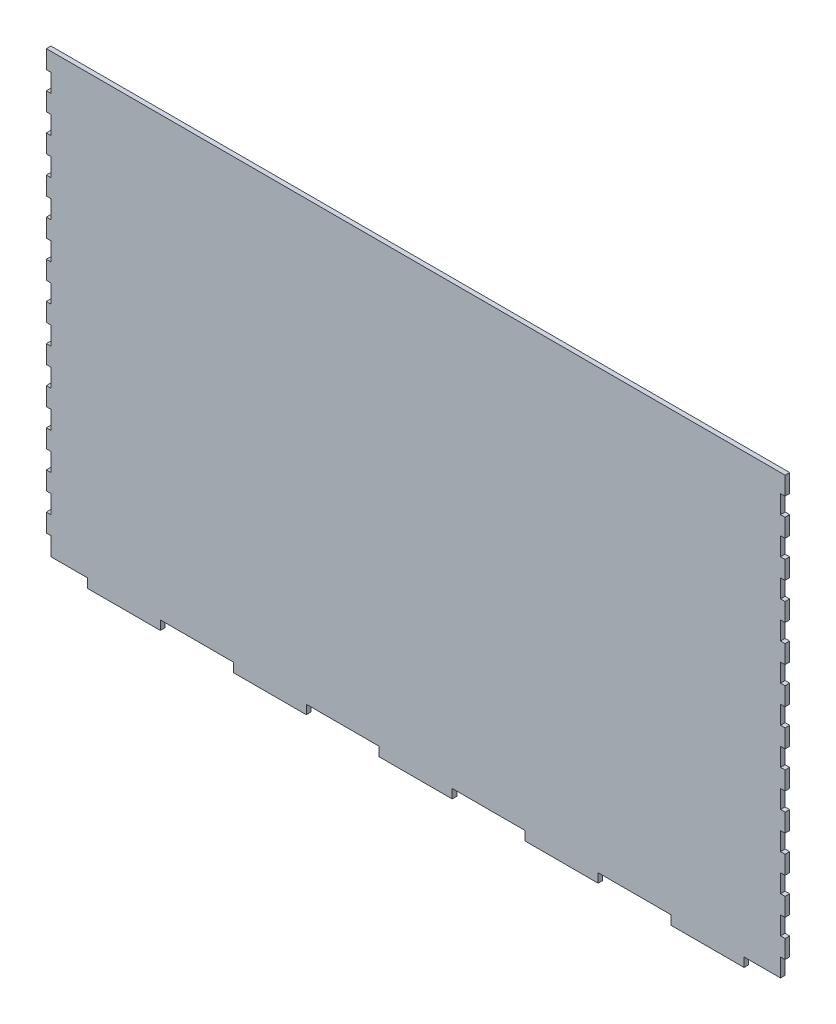
SolidWorks part; units mm, degrees
ref_plane "Front Plane" through (0, 0, 0) normal (0, 0, 1) x (1, 0, 0)
ref_plane "Top Plane" through (0, 0, 0) normal (0, 1, 0) x (1, 0, 0)
ref_plane "Right Plane" through (0, 0, 0) normal (1, 0, 0) x (0, 0, -1)
sketch "Sketch1" plane through (0, 0, 0) normal (0, 0, 1) x (1, 0, 0)
  line L0 (0, 0) -> (508, 0)
  line L1 (508, 0) -> (508, 304.8)
  line L2 (508, 304.8) -> (0, 304.8)
  line L3 (0, 304.8) -> (0, 0)
  line L4 (254, 304.8) -> (254, 0) construction
  line L5 (0, 304.8) -> (-3.175, 304.8)
  line L6 (-3.175, 304.8) -> (-3.175, 292.1)
  line L7 (-3.175, 292.1) -> (0, 292.1)
  line L8 (25.4, 0) -> (25.4, -6.35)
  line L9 (25.4, -6.35) -> (76.2, -6.35)
  line L10 (76.2, -6.35) -> (76.2, 0)
  line L13 (0, 279.4) -> (-3.175, 279.4)
  line L14 (-3.175, 279.4) -> (-3.175, 266.7)
  line L15 (-3.175, 266.7) -> (0, 266.7)
  line L17 (0, 254) -> (-3.175, 254)
  line L18 (-3.175, 254) -> (-3.175, 241.3)
  line L19 (-3.175, 241.3) -> (0, 241.3)
  line L21 (0, 228.6) -> (-3.175, 228.6)
  line L22 (-3.175, 228.6) -> (-3.175, 215.9)
  line L23 (-3.175, 215.9) -> (0, 215.9)
  line L25 (0, 203.2) -> (-3.175, 203.2)
  line L26 (-3.175, 203.2) -> (-3.175, 190.5)
  line L27 (-3.175, 190.5) -> (0, 190.5)
  line L29 (0, 177.8) -> (-3.175, 177.8)
  line L30 (-3.175, 177.8) -> (-3.175, 165.1)
  line L31 (-3.175, 165.1) -> (0, 165.1)
  line L33 (0, 152.4) -> (-3.175, 152.4)
  line L34 (-3.175, 152.4) -> (-3.175, 139.7)
  line L35 (-3.175, 139.7) -> (0, 139.7)
  line L37 (0, 127) -> (-3.175, 127)
  line L38 (-3.175, 127) -> (-3.175, 114.3)
  line L39 (-3.175, 114.3) -> (0, 114.3)
  line L41 (0, 101.6) -> (-3.175, 101.6)
  line L42 (-3.175, 101.6) -> (-3.175, 88.9)
  line L43 (-3.175, 88.9) -> (0, 88.9)
  line L45 (0, 76.2) -> (-3.175, 76.2)
  line L46 (-3.175, 76.2) -> (-3.175, 63.5)
  line L47 (-3.175, 63.5) -> (0, 63.5)
  line L49 (0, 50.8) -> (-3.175, 50.8)
  line L50 (-3.175, 50.8) -> (-3.175, 38.1)
  line L51 (-3.175, 38.1) -> (0, 38.1)
  line L53 (0, 25.4) -> (-3.175, 25.4)
  line L54 (-3.175, 25.4) -> (-3.175, 12.7)
  line L55 (-3.175, 12.7) -> (0, 12.7)
  line L57 (0, 304.8) -> (0, 279.4) construction
  line L59 (127, 0) -> (127, -6.35)
  line L60 (127, -6.35) -> (177.8, -6.35)
  line L61 (177.8, -6.35) -> (177.8, 0)
  line L63 (228.6, 0) -> (228.6, -6.35)
  line L64 (228.6, -6.35) -> (279.4, -6.35)
  line L65 (279.4, -6.35) -> (279.4, 0)
  line L67 (330.2, 0) -> (330.2, -6.35)
  line L68 (330.2, -6.35) -> (381, -6.35)
  line L69 (381, -6.35) -> (381, 0)
  line L70 (76.2, 0) -> (177.8, 0) construction
  line L72 (431.8, 0) -> (431.8, -6.35)
  line L73 (431.8, -6.35) -> (482.6, -6.35)
  line L74 (482.6, -6.35) -> (482.6, 0)
  line L76 (511.175, 12.7) -> (508, 12.7)
  line L77 (511.175, 25.4) -> (511.175, 12.7)
  line L78 (508, 25.4) -> (511.175, 25.4)
  line L80 (511.175, 38.1) -> (508, 38.1)
  line L81 (511.175, 50.8) -> (511.175, 38.1)
  line L82 (508, 50.8) -> (511.175, 50.8)
  line L84 (511.175, 63.5) -> (508, 63.5)
  line L85 (511.175, 76.2) -> (511.175, 63.5)
  line L86 (508, 76.2) -> (511.175, 76.2)
  line L88 (511.175, 88.9) -> (508, 88.9)
  line L89 (511.175, 101.6) -> (511.175, 88.9)
  line L90 (508, 101.6) -> (511.175, 101.6)
  line L92 (511.175, 114.3) -> (508, 114.3)
  line L93 (511.175, 127) -> (511.175, 114.3)
  line L94 (508, 127) -> (511.175, 127)
  line L96 (511.175, 139.7) -> (508, 139.7)
  line L97 (511.175, 152.4) -> (511.175, 139.7)
  line L98 (508, 152.4) -> (511.175, 152.4)
  line L100 (511.175, 165.1) -> (508, 165.1)
  line L101 (511.175, 177.8) -> (511.175, 165.1)
  line L102 (508, 177.8) -> (511.175, 177.8)
  line L104 (511.175, 190.5) -> (508, 190.5)
  line L105 (511.175, 203.2) -> (511.175, 190.5)
  line L106 (508, 203.2) -> (511.175, 203.2)
  line L108 (511.175, 215.9) -> (508, 215.9)
  line L109 (511.175, 228.6) -> (511.175, 215.9)
  line L110 (508, 228.6) -> (511.175, 228.6)
  line L112 (511.175, 241.3) -> (508, 241.3)
  line L113 (511.175, 254) -> (511.175, 241.3)
  line L114 (508, 254) -> (511.175, 254)
  line L116 (511.175, 266.7) -> (508, 266.7)
  line L117 (511.175, 279.4) -> (511.175, 266.7)
  line L118 (508, 279.4) -> (511.175, 279.4)
  line L120 (511.175, 292.1) -> (508, 292.1)
  line L121 (511.175, 304.8) -> (511.175, 292.1)
  line L122 (508, 304.8) -> (511.175, 304.8)
  dimension "D1" = 508
  dimension "D2" = 304.8
  dimension "D3" = 3.175
  dimension "D4" = 12.7
  dimension "D5" = 6.35
  dimension "D6" = 50.8
  dimension "D7" = 25.4
  dimension "D9" = 25.4
  dimension "D11" = 101.6
  dimension "D8" = 12
  dimension "D10" = 5
extrude "Boss-Extrude1" add sketch "Sketch1" along normal blind 3.175 contours L2 L3 L0 L1 | L9 L10 L0 L8 | L60 L61 L0 L59 | L64 L65 L0 L63 | L68 L69 L0 L67 | L73 L74 L0 L72 | L54 L55 L3 L53 | L50 L51 L3 L49 | L46 L47 L3 L45 | L42 L43 L3 L41 | L38 L39 L3 L37 | L34 L35 L3 L33 | L30 L31 L3 L29 | L26 L27 L3 L25 | L22 L23 L3 L21 | L18 L19 L3 L17 | L14 L15 L3 L13 | L6 L7 L3 L5 | L78 L1 L76 L77 | L82 L1 L80 L81 | L86 L1 L84 L85 | L90 L1 L88 L89 | L98 L1 L96 L97 | L94 L1 L92 L93 | L102 L1 L100 L101 | L106 L1 L104 L105 | L110 L1 L108 L109 | L114 L1 L112 L113 | L118 L1 L116 L117 | L122 L1 L120 L121 region at (254, 152.4, 0) region at (50.8, -3.175, 0) region at (-1.5875, 19.05, 0) region at (152.4, -3.175, 0) region at (-1.5875, 44.45, 0) region at (254, -3.175, 0) region at (-1.5875, 69.85, 0) region at (355.6, -3.175, 0) region at (-1.5875, 95.25, 0) region at (457.2, -3.175, 0) region at (-1.5875, 120.65, 0) region at (-1.5875, 146.05, 0) region at (509.5875, 19.05, 0) region at (-1.5875, 171.45, 0) region at (509.5875, 44.45, 0) region at (-1.5875, 196.85, 0) region at (509.5875, 69.85, 0) region at (-1.5875, 222.25, 0) region at (509.5875, 95.25, 0) region at (-1.5875, 247.65, 0) region at (509.5875, 120.65, 0) region at (-1.5875, 273.05, 0) region at (509.5875, 146.05, 0) region at (-1.5875, 298.45, 0) region at (509.5875, 171.45, 0) region at (509.5875, 298.45, 0) region at (509.5875, 196.85, 0) region at (509.5875, 273.05, 0) region at (509.5875, 222.25, 0) region at (509.5875, 247.65, 0)
equation "\"wall_thickness\" = 0.125in"
equation "\"base_thickness\" = 0.25in"
equation "\"D3@Sketch1\"=\"wall_thickness\""
equation "\"D5@Sketch1\"=\"base_thickness\""
equation "\"D1@Boss-Extrude1\"=\"wall_thickness\""
